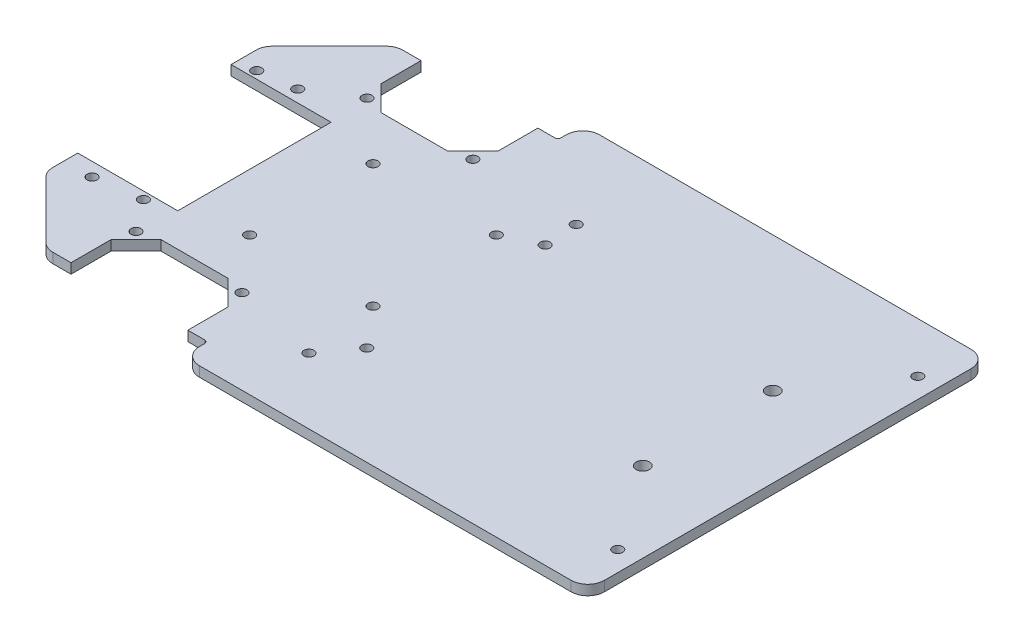
SolidWorks part; units mm, degrees
ref_plane "Front Plane" through (0, 0, 0) normal (0, 0, 1) x (1, 0, 0)
ref_plane "Top Plane" through (0, 0, 0) normal (0, 1, 0) x (1, 0, 0)
ref_plane "Right Plane" through (0, 0, 0) normal (1, 0, 0) x (0, 0, -1)
sketch "Sketch1" plane through (0, 0, 0) normal (0, 1, 0) x (1, 0, 0)
  line L0 (190, 0) -> (0, 0) construction
  line L1 (0, -60) -> (190, -60)
  line L2 (0, -60) -> (0, 60)
  line L3 (0, 60) -> (190, 60)
  line L4 (190, -60) -> (190, 60)
  line L5 (0, -32.5266) -> (27.4734, -60)
  line L6 (30, 23) -> (0, 23) construction
  line L7 (30, 23) -> (30, -23) construction
  line L8 (30, -23) -> (0, -23) construction
  line L9 (0, 23) -> (0, -23)
  line L10 (30, 23) -> (0, -23) construction
  line L11 (30, -23) -> (0, 23) construction
  line L12 (19.9734, -52.5) -> (27.4734, -52.5) construction
  line L13 (68.5266, -52.5) -> (68.5266, -60) construction
  line L14 (35, -33) -> (27.4734, -40.5266) construction
  line L15 (27.4734, -52.5) -> (27.4734, -40.5266) construction
  line L16 (27.4734, -40.5266) -> (27.4734, -52.5) construction
  line L17 (0, 32.5266) -> (27.4734, 60)
  line L18 (35, -33) -> (55, -33) construction
  line L19 (55, -33) -> (62.5266, -40.5266) construction
  line L20 (62.5266, -52.5) -> (68.5266, -52.5) construction
  line L21 (47.5, -37) -> (42.5, -37) construction
  line L22 (45, -37) -> (45, -33) construction
  line L23 (45, -56.5) -> (45, -52.5) construction
  line L24 (39.4, -56.5) -> (50.6, -56.5) construction
  line L25 (27.4734, -52.5) -> (62.5266, -52.5) construction
  line L27 (62.5266, -40.5266) -> (62.5266, -52.5) construction
  point P7 (0, 0)
  point P8 (15, 0)
  dimension "D1" = 120
  dimension "D2" = 190
  dimension "D3" = 30
  dimension "D4" = 23
  dimension "D5" = 10
  dimension "D6" = 20
  dimension "D7" = 45
  dimension "D8" = 45
  dimension "D9" = 45
  dimension "D10" = 7.5
  dimension "D11" = 6
extrude "Boss-Extrude1" add sketch "Sketch1" along normal blind 3 contours L7 L8 L2 L1 L4 L3 L6 region at (97.9391, 0, 0)
sketch "Sketch4" plane through (0, 0, 0) normal (0, 1, 0) x (1, 0, 0)
  line L0 (68.5266, -60) -> (68.5266, -52.5)
  line L1 (68.5266, -52.5) -> (62.5266, -52.5)
  line L2 (62.5266, -52.5) -> (62.5266, -40.5266)
  line L3 (62.5266, -40.5266) -> (55, -33)
  line L4 (55, -33) -> (35, -33)
  line L5 (35, -33) -> (27.4734, -40.5266)
  line L6 (27.4734, -40.5266) -> (27.4734, -52.5)
  line L7 (27.4734, -52.5) -> (19.9734, -52.5)
  line L8 (19.9734, -52.5) -> (27.4734, -60)
  line L9 (27.4734, -60) -> (68.5266, -60)
  line L10 (0, 0) -> (190, 0) construction
  line L11 (190, -60) -> (190, 60) construction
  line L12 (27.4734, 60) -> (68.5266, 60)
  line L13 (19.9734, 52.5) -> (27.4734, 60)
  line L14 (27.4734, 52.5) -> (19.9734, 52.5)
  line L15 (27.4734, 40.5266) -> (27.4734, 52.5)
  line L16 (35, 33) -> (27.4734, 40.5266)
  line L17 (55, 33) -> (35, 33)
  line L18 (62.5266, 40.5266) -> (55, 33)
  line L19 (62.5266, 52.5) -> (62.5266, 40.5266)
  line L20 (68.5266, 52.5) -> (62.5266, 52.5)
  line L21 (68.5266, 60) -> (68.5266, 52.5)
  line L23 (30, 23) -> (0, 23)
  line L24 (30, 23) -> (30, -23)
  line L25 (30, -23) -> (0, -23)
  line L26 (0, 23) -> (0, -23)
extrude "Cut-Extrude1" cut sketch "Sketch4" along normal up to surface (3 mm away) up to face at (72.4911, 3, 0)
fillet "Fillet1" radius 5 8 edges at (19.9734, 1.5, -52.5) (0, 1.5, -32.5266) (68.5266, 1.5, -60) (190, 1.5, -60) (190, 1.5, 60) (0, 1.5, 32.5266) (19.9734, 1.5, 52.5) (68.5266, 1.5, 60)
fillet "Fillet2" radius 1 2 edges at (68.5266, 1.5, -52.5) (68.5266, 1.5, 52.5)
sketch "Sketch5" plane through (0, 0, 0) normal (0, 1, 0) x (1, 0, 0)
  circle A0 centre (47.0626, -18.5) radius 1.5 construction
  circle A1 centre (47.0626, -18.5) radius 1.5
  circle A2 centre (84.0626, -18.5) radius 1.5 construction
  circle A3 centre (84.0626, -18.5) radius 1.5
  circle A4 centre (84.0626, 18.5) radius 1.5 construction
  circle A5 centre (84.0626, 18.5) radius 1.5
  circle A6 centre (47.0626, 18.5) radius 1.5 construction
  circle A7 centre (47.0626, 18.5) radius 1.5
  circle A8 centre (94, 23.2195) radius 1.5 construction
  circle A9 centre (94, 23.2195) radius 1.5
  circle A10 centre (93.3054, 33.2195) radius 1.5 construction
  circle A11 centre (93.3054, 33.2195) radius 1.5
  circle A12 centre (29.1154, 34.642) radius 1.5 construction
  circle A13 centre (60.8846, 34.642) radius 1.5 construction
  circle A14 centre (8.3674, -27.0854) radius 1.5 construction
  circle A15 centre (16.3794, 26.6064) radius 1.5 construction
  circle A16 centre (94, -30.308) radius 1.5 construction
  circle A17 centre (86.6598, -40.308) radius 1.5 construction
  circle A18 centre (29.1154, 34.642) radius 1.5
  circle A19 centre (60.8846, 34.642) radius 1.5
  circle A20 centre (8.3674, -27.0854) radius 1.5
  circle A21 centre (16.3794, 26.6064) radius 1.5
  circle A22 centre (94, -30.308) radius 1.5
  circle A23 centre (86.6598, -40.308) radius 1.5
  circle A24 centre (184, -45) radius 1.5 construction
  circle A25 centre (184, 45) radius 1.5 construction
  circle A26 centre (184, -45) radius 1.5
  circle A27 centre (184, 45) radius 1.5
  circle A28 centre (166, -19.5) radius 2 construction
  circle A29 centre (166, 19.5) radius 2 construction
  circle A30 centre (166, -19.5) radius 2
  circle A31 centre (166, 19.5) radius 2
  circle A32 centre (29.1154, -34.642) radius 1.5 construction
  circle A33 centre (60.8846, -34.642) radius 1.5 construction
  circle A34 centre (29.1154, -34.642) radius 1.5
  circle A35 centre (60.8846, -34.642) radius 1.5
  circle A36 centre (21.9337, -25.25) radius 1.5 construction
  circle A37 centre (5.4397, 25.25) radius 1.5 construction
  circle A38 centre (21.9337, -25.25) radius 1.5
  circle A39 centre (5.4397, 25.25) radius 1.5
extrude "Cut-Extrude2" cut sketch "Sketch5" along normal up to surface (3 mm away) up to face at (55.2686, 3, 0)
